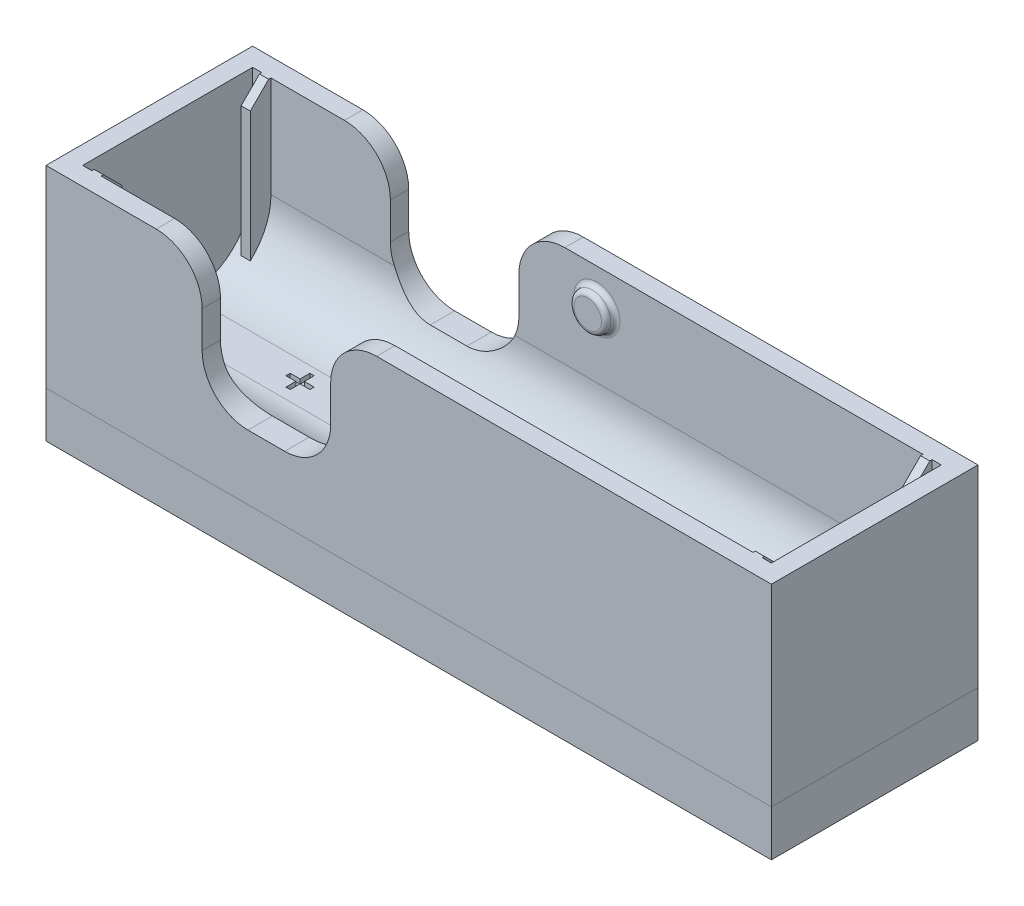
SolidWorks part; units mm, degrees
other "Проставка"
other "блок акума"
ref_plane "Спереди" through (0, 0, 0) normal (0, 0, 1) x (1, 0, 0)
ref_plane "Сверху" through (0, 0, 0) normal (0, 1, 0) x (1, 0, 0)
ref_plane "Справа" through (0, 0, 0) normal (1, 0, 0) x (0, 0, -1)
other "Configuration Table"
sketch "Эскиз1" plane through (0, 0, 0) normal (0, 1, 0) x (1, 0, 0)
  line L0 (0, 0) -> (97.2692, 0) construction
  line L1 (36.5, 9.25) -> (36.5, 7)
  line L2 (-37.5, -9.25) -> (37.5, -9.25)
  line L3 (-37.5, -9.25) -> (-37.5, 9.25)
  line L4 (-37.5, 9.25) -> (37.5, 9.25)
  line L5 (37.5, -9.25) -> (37.5, 9.25)
  line L6 (-37.5, -9.25) -> (37.5, 9.25) construction
  line L7 (-37.5, 9.25) -> (37.5, -9.25) construction
  line L8 (35.5, 9.25) -> (35.5, 7)
  line L9 (-36.5, 9.25) -> (-36.5, 7)
  line L10 (-35.5, 9.25) -> (-35.5, 7)
  line L11 (-36.5, 7) -> (-35.5, 7)
  line L12 (-36.5, -7) -> (-35.5, -7)
  line L13 (-35.5, -7) -> (-35.5, -9.25)
  line L14 (-36.5, -7) -> (-36.5, -9.25)
  line L15 (35.5, 7) -> (36.5, 7)
  line L16 (35.5, -7) -> (36.5, -7)
  line L17 (35.5, -7) -> (35.5, -9.25)
  line L18 (36.5, -7) -> (36.5, -9.25)
  line L19 (-36.5, 2.5) -> (-36.5, -2.5)
  line L20 (36.5, 2.5) -> (36.5, -2.5)
  line L21 (-37.5, 2.5) -> (-36.5, 2.5)
  line L22 (-37.5, -2.5) -> (-36.5, -2.5)
  line L23 (36.5, 2.5) -> (37.5, 2.5)
  line L24 (36.5, -2.5) -> (37.5, -2.5)
  line L25 (-39.5, 11.25) -> (39.5, 11.25)
  line L26 (39.5, -11.25) -> (39.5, 11.25)
  line L27 (-39.5, -11.25) -> (39.5, -11.25)
  line L28 (-39.5, -11.25) -> (-39.5, 11.25)
  point P1 (0, 0)
  dimension "D1" = 18.5
  dimension "D2" = 75
  dimension "D3" = 1
  dimension "D4" = 1
  dimension "D5" = 1
  dimension "D6" = 1
  dimension "D7" = 7
  dimension "D8" = 2.5
  dimension "D9" = 2.5
  dimension "D10" = 1
  dimension "D11" = 1
  dimension "D12" = 2
extrude "Бобышка-Вытянуть1" add sketch "Эскиз1" along normal blind 18 contours L28 L27 L26 L25 L5 L2 L3 L4 | L9 L11 L10 L4 | L12 L14 L2 L13 | L8 L15 L1 L4 | L18 L16 L17 L2 region at (36, 0, -8.125) region at (-36, 0, -8.125) region at (36, 0, 8.125) region at (-36, 0, 8.125) region at (0, 0, -10.4286)
extrude "Бобышка-Вытянуть2" add sketch "Эскиз1<4>" against normal blind 3 contours L28 L27 L26 L25 L5 L2 L3 L4 | L24 L20 L23 L5 L4 L1 L15 L8 L10 L11 L9 L3 L21 L19 L22 L2 L14 L12 L13 L17 L16 L18 | L12 L14 L2 L13 | L9 L11 L10 L4 | L18 L16 L17 L2 | L8 L15 L1 L4 region at (0, 0, 0) region at (36, 0, -8.125) region at (-36, 0, -8.125) region at (36, 0, 8.125) region at (-36, 0, 8.125) region at (0, 0, -10.4286)
sketch "Эскиз1<4>" plane through (0, 0, 0) normal (0, 1, 0) x (1, 0, 0) same geometry as "Эскиз1"
fillet "Скругление1" radius 7 2 edges at (0, 0, 9.25) (0, 0, -9.25)
sketch "Эскиз2" plane through (0, 0, 0) normal (0, 1, 0) x (1, 0, 0)
  text T0 "+"
  text T1 "<b>-</b>"
extrude "Вырез-Вытянуть1" cut sketch "Эскиз2" against normal blind 0.5
sketch "Эскиз3" plane through (0, 0, 11.25) normal (0, 0, 1) x (1, 0, 0)
  line L0 (-39.5, 18) -> (39.5, 18) construction
  line L1 (-21.5, 18) -> (-8.5, 18)
  line L2 (-22.4975, 13) -> (-22.4975, 9.0356)
  line L3 (-17.4975, 4.0356) -> (-13.4975, 4.0356)
  line L4 (-8.4975, 13) -> (-8.4975, 9.0356)
  line L5 (-27.5, 18) -> (-21.5, 18)
  line L6 (-8.5, 18) -> (-3.4975, 18)
  arc A0 (-13.4975, 4.0356) -> (-8.4975, 9.0356) centre (-13.4975, 9.0356) ccw
  arc A1 (-22.4975, 9.0356) -> (-17.4975, 4.0356) centre (-17.4975, 9.0356) ccw
  arc A2 (-3.4975, 18) -> (-8.4975, 13) centre (-3.4975, 13) ccw
  arc A3 (-27.5, 18) -> (-22.4975, 13) centre (-27.4975, 13) cw
  point P9 (-8.4975, 4.0356)
  point P12 (-22.4975, 4.0356)
  dimension "D4" = 5
  dimension "D5" = 5
  dimension "D1" = 14
  dimension "D2" = 14
  dimension "D3" = 18
extrude "Вырез-Вытянуть2" cut sketch "Эскиз3" against normal blind 30.5
chamfer "Фаска1" distance 2 angle 45 4 edges at (36, 18, 7) (36, 18, -7) (-36, 18, 7) (-36, 18, -7)
sketch "Эскиз4" plane through (0, 0, 9.25) normal (0, 0, -1) x (-1, 0, 0)
  line L0 (0, 0) -> (0, 28.1341) construction
  circle A0 centre (0, 14) radius 2
  dimension "D1" = 4
  dimension "D2" = 14
extrude "Бобышка-Вытянуть4" add sketch "Эскиз4" along normal blind 1
sketch "Эскиз5" plane through (0, 0, -9.25) normal (0, 0, 1) x (1, 0, 0)
  line L0 (0, 0) -> (0, 24.5494) construction
  circle A0 centre (0, 14) radius 2
  dimension "D1" = 4
  dimension "D2" = 14
extrude "Бобышка-Вытянуть5" add sketch "Эскиз5" along normal blind 1
fillet "Скругление3" radius 0.5 4 edges at (-2, 14, 8.25) (-2, 14, 9.25) (2, 14, -8.25) (-2, 14, -9.25)
sketch "Эскиз6" plane through (0, -3, 0) normal (0, -1, 0) x (1, 0, 0)
  line L0 (-37.5, 6.25) -> (-37.5, -6.25)
  line L1 (-39.5, 11.25) -> (39.5, 11.25)
  line L2 (-39.5, 11.25) -> (-39.5, -11.25)
  line L3 (-39.5, -11.25) -> (39.5, -11.25)
  line L4 (39.5, 11.25) -> (39.5, -11.25)
  line L5 (-34.5, -9.25) -> (34.5, -9.25)
  line L6 (37.5, 6.25) -> (37.5, -6.25)
  line L7 (-34.5, 9.25) -> (34.5, 9.25)
  line L8 (-39.5, 6.25) -> (-34.5, 11.25) construction
  line L9 (-39.5, 11.25) -> (-34.5, 11.25)
  line L10 (-39.5, 11.25) -> (-39.5, 6.25)
  line L11 (-39.5, 6.25) -> (-36.5, 6.25)
  line L12 (-34.5, 11.25) -> (-34.5, 8.25)
  line L13 (-39.5, -11.25) -> (-34.5, -11.25)
  line L14 (-39.5, -11.25) -> (-39.5, -6.25)
  line L15 (-39.5, -6.25) -> (-36.5, -6.25)
  line L16 (-34.5, -11.25) -> (-34.5, -8.25)
  line L17 (39.5, -11.25) -> (34.5, -11.25)
  line L18 (39.5, -11.25) -> (39.5, -6.25)
  line L19 (39.5, -6.25) -> (36.5, -6.25)
  line L20 (34.5, -11.25) -> (34.5, -8.25)
  line L21 (39.5, 11.25) -> (34.5, 11.25)
  line L22 (39.5, 11.25) -> (39.5, 6.25)
  line L23 (39.5, 6.25) -> (36.5, 6.25)
  line L24 (34.5, 11.25) -> (34.5, 8.25)
  line L25 (-37.5, 9.25) -> (37.5, 9.25) construction
  line L26 (-37.5, 9.25) -> (-37.5, -9.25) construction
  line L27 (-37.5, -9.25) -> (37.5, -9.25) construction
  line L28 (37.5, 9.25) -> (37.5, -9.25) construction
  line L29 (-39.5, -6.25) -> (-34.5, -11.25) construction
  line L30 (34.5, 11.25) -> (39.5, 6.25) construction
  line L31 (34.5, -11.25) -> (39.5, -6.25) construction
  arc A0 (36.5, -6.25) -> (34.5, -8.25) centre (36.5, -8.25) ccw
  arc A1 (34.5, 8.25) -> (36.5, 6.25) centre (36.5, 8.25) ccw
  arc A2 (-34.5, -8.25) -> (-36.5, -6.25) centre (-36.5, -8.25) ccw
  arc A3 (-34.5, 8.25) -> (-36.5, 6.25) centre (-36.5, 8.25) cw
  circle A4 centre (-37, 8.75) radius 0.5
  circle A5 centre (37, 8.75) radius 0.5
  circle A6 centre (37, -8.75) radius 0.5
  circle A7 centre (-37, -8.75) radius 0.5
  point P38 (-34.5, 6.25)
  point P39 (-37, 8.75)
  point P40 (-37, -8.75)
  point P41 (37, -8.75)
  point P42 (37, 8.75)
  line M9 (37.5, 2.5) -> (37.5, -2.5)
  line M16 (-37.5, -2.5) -> (-37.5, 2.5)
  line M17 (-39.5, 11.25) -> (-39.5, -11.25)
  line M18 (-39.5, -11.25) -> (39.5, -11.25)
  line M19 (39.5, -11.25) -> (39.5, 11.25)
  line M20 (39.5, 11.25) -> (-39.5, 11.25)
  dimension "D3" = 2
  dimension "D4" = 1
  dimension "D2" = 5
  dimension "D1" = 2
extrude "Бобышка-Вытянуть6" add sketch "Эскиз6" along normal blind 5 separate body contours A3 L12 L1 L11 A4 M17 | L24 L1 L12 L7 | L2 L15 L0 L11 M16 | L16 A2 L15 A7 M17 M18 | L3 L20 L5 L16 | L24 A1 L23 A5 M19 M20 | L4 L23 L6 L19 M9 | L19 A0 L20 A6 M18 M19 region at (-38.5, -3, 0) region at (-38.5, -3, 6.3207) region at (-38.5, -3, -6.3207) region at (0, -3, 10.25) region at (37, -3, 11.1793) region at (0, -3, -10.25) region at (34.5707, -3, -10.25) region at (38.5, -3, 0)
extrude "Вырез-Вытянуть3" cut sketch "Эскиз6<3>" against normal blind 3 contours A7 | A4 | A6 | A5 region at (-37, -3, 8.75) region at (37, -3, 8.75) region at (37, -3, -8.75) region at (-37, -3, -8.75)
sketch "Эскиз6<3>" plane through (0, -3, 0) normal (0, -1, 0) x (1, 0, 0) same geometry as "Эскиз6"
